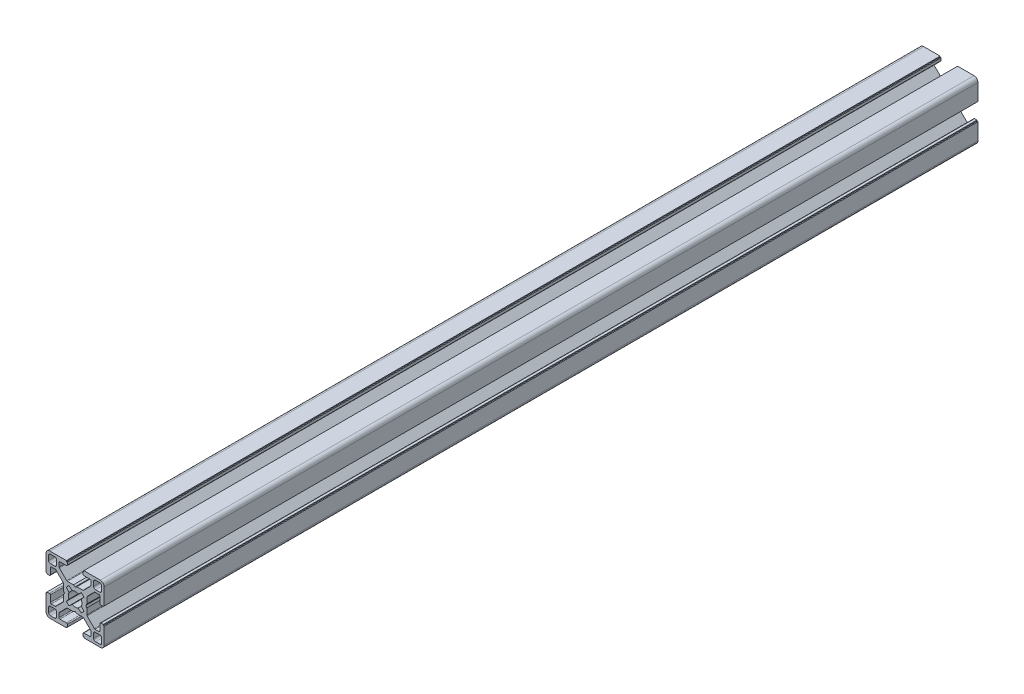
SolidWorks part; units mm, degrees
ref_plane "Front Plane" through (0, 0, 0) normal (0, 0, 1) x (1, 0, 0)
ref_plane "Top Plane" through (0, 0, 0) normal (0, 1, 0) x (1, 0, 0)
ref_plane "Right Plane" through (0, 0, 0) normal (1, 0, 0) x (0, 0, -1)
sketch "Sketch1" plane through (0, 0, 0) normal (0, 0, 1) x (1, 0, 0)
  line L0 (-15, 0) -> (15, 0) construction
  line L1 (0, -15) -> (0, 15) construction
  line L2 (-4.5, 15) -> (4.5, 15) construction
  line L3 (-4, -15) -> (4, -15) construction
  line L4 (-4.5, 15) -> (-4.5, 14.5)
  line L5 (-4.5, 14.5) -> (-4, 14.5)
  line L6 (-4, 14.5) -> (-4, 13.29)
  line L7 (-4.5, 12.79) -> (-7.7675, 12.79)
  line L8 (-8.2675, 12.29) -> (-8.2675, 10.2707)
  line L9 (-8.1211, 9.9171) -> (-4.3504, 6.1464)
  line L10 (-3.9968, 6) -> (0, 6)
  line L11 (0, 0) -> (-15, 15) construction
  line L12 (-4.5, 15) -> (-12.968, 15)
  line L14 (-12.705, 9.5135) -> (-10.5135, 9.5135)
  line L15 (-13.705, 10.5135) -> (-13.705, 12.705)
  line L16 (-12.705, 13.705) -> (-10.5135, 13.705)
  line L17 (-9.5135, 10.5135) -> (-9.5135, 12.705)
  line L18 (-13.705, 9.5135) -> (-9.5135, 13.705) construction
  line L19 (-13.705, 13.705) -> (-9.5135, 9.5135) construction
  line L20 (-3.1568, 4.5038) -> (-1.5303, 3.1477) construction
  line L21 (-4.5038, 3.1568) -> (-3.1477, 1.5303) construction
  line L22 (-6, 3.9968) -> (-6, 0)
  line L23 (-9.9171, 8.1211) -> (-6.1464, 4.3504)
  line L24 (-15, 4.5) -> (-15, 12.968)
  line L25 (-12.29, 8.2675) -> (-10.2707, 8.2675)
  line L26 (-12.79, 4.5) -> (-12.79, 7.7675)
  line L27 (-14.5, 4) -> (-13.29, 4)
  line L28 (-14.5, 4.5) -> (-14.5, 4)
  line L29 (-15, 4.5) -> (-14.5, 4.5)
  circle A0 centre (0, 0) radius 3.5
  arc A1 (-12.968, 15) -> (-15, 12.968) centre (-12.968, 12.968) ccw
  circle A2 centre (0, 0) radius 5.5 construction
  arc A3 (-10.5135, 9.5135) -> (-9.5135, 10.5135) centre (-10.5135, 10.5135) ccw
  arc A4 (-13.705, 12.705) -> (-12.705, 13.705) centre (-12.705, 12.705) cw
  arc A5 (-10.5135, 13.705) -> (-9.5135, 12.705) centre (-10.5135, 12.705) cw
  arc A6 (-12.705, 9.5135) -> (-13.705, 10.5135) centre (-12.705, 10.5135) cw
  arc A7 (-12.79, 4.5) -> (-13.29, 4) centre (-13.29, 4.5) cw
  arc A8 (-12.29, 8.2675) -> (-12.79, 7.7675) centre (-12.29, 7.7675) ccw
  arc A9 (-9.9171, 8.1211) -> (-10.2707, 8.2675) centre (-10.2707, 7.7675) ccw
  arc A10 (-6, 3.9968) -> (-6.1464, 4.3504) centre (-6.5, 3.9968) ccw
  arc A11 (-4.3504, 6.1464) -> (-3.9968, 6) centre (-3.9968, 6.5) ccw
  arc A12 (-4, 13.29) -> (-4.5, 12.79) centre (-4.5, 13.29) cw
  arc A13 (-7.7675, 12.79) -> (-8.2675, 12.29) centre (-7.7675, 12.29) ccw
  arc A14 (-8.2675, 10.2707) -> (-8.1211, 9.9171) centre (-7.7675, 10.2707) ccw
  point P4 (0, 0)
  point P8 (0, 0)
  point P13 (0, 15)
  point P15 (0, -15)
  point P16 (0, 6)
  point P23 (-11.6092, 11.6093)
  point P26 (0, 6)
  point P62 (-12.79, 4)
  point P65 (-12.79, 8.2675)
  point P68 (-10.0636, 8.2675)
  point P71 (-6, 4.2039)
  point P74 (-4.2039, 6)
  point P77 (-4, 12.79)
  point P80 (-8.2675, 12.79)
  point P83 (-8.2675, 10.0636)
  dimension "Center Hole Diameter" = 7
  dimension "D11" = 2.032
  dimension "D9" = 11
  dimension "D13" = 1
  dimension "D14" = 0.5
  dimension "Rail Height" = 30
  dimension "Rail Width" = 30
  dimension "T-Slot Width" = 8
  dimension "T-Slot Depth" = 9
  dimension "D1" = 9
  dimension "D2" = 45
  dimension "D3" = 8
  dimension "D4" = 2.21
  dimension "D5" = 16.535
  dimension "D7" = 2.54
  dimension "D6" = 1.295
  dimension "D8" = 1.246
  dimension "D10" = 10.36
  dimension "D12" = 1.905
sketch "Sketch2" plane through (0, 0, 0) normal (1, 0, 0) x (0, 0, -1)
  line L0 (-76.2, 0) -> (76.2, 0) construction
  line L2 (0, -15) -> (0, 15) construction
  line L3 (0, -15) -> (0, 15) construction
  line L4 (-76.2, -15) -> (-76.2, 15) construction
  line L5 (76.2, -15) -> (76.2, 15) construction
  point P0 (-38.7, 0)
  point P3 (0, 0)
  point P4 (38.7, 0)
  point P12 (-76.2, 0)
  point P14 (76.2, 0)
  dimension "Length" = 152.4
  dimension "D1" = 37.5
sketch "Sketch3" plane through (0, 0, 0) normal (0, 0, 1) x (1, 0, 0)
  line L0 (-4.5038, 3.1568) -> (-3.1477, 1.5303)
  line L1 (0, 3.5) -> (0, 5.5)
  line L2 (-5.5, 0) -> (-3.5, 0)
  line L7 (-6, 3.9968) -> (-6, 0) construction
  line L31 (-9.9171, 8.1211) -> (-6.1464, 4.3504) construction
  line L117 (-12.29, 8.2675) -> (-10.2707, 8.2675) construction
  line L118 (-12.79, 4.5) -> (-12.79, 7.7675) construction
  line L157 (-12.705, 9.5135) -> (-10.5135, 9.5135)
  line L158 (-9.5135, 10.5135) -> (-9.5135, 12.705)
  line L163 (-10.5135, 13.705) -> (-12.705, 13.705)
  line L164 (-13.705, 12.705) -> (-13.705, 10.5135)
  line L165 (-12.705, 9.5135) -> (-10.5135, 9.5135)
  line L166 (-9.5135, 10.5135) -> (-9.5135, 12.705)
  line L167 (-10.5135, 13.705) -> (-12.705, 13.705)
  line L168 (-13.705, 12.705) -> (-13.705, 10.5135)
  line L169 (-14.5, 4) -> (-13.29, 4) construction
  line L170 (-14.5, 4.5) -> (-14.5, 4) construction
  line L171 (-15, 4.5) -> (-14.5, 4.5) construction
  line L172 (-15, 4.5) -> (-15, 12.968) construction
  line L173 (-4.5, 15) -> (-12.968, 15) construction
  line L174 (-4.5, 15) -> (-4.5, 14.5) construction
  line L175 (-4.5, 14.5) -> (-4, 14.5) construction
  line L176 (-4, 14.5) -> (-4, 13.29) construction
  line L177 (-4.5, 12.79) -> (-7.7675, 12.79) construction
  line L178 (-8.2675, 12.29) -> (-8.2675, 10.2707) construction
  line L179 (-8.1211, 9.9171) -> (-4.3504, 6.1464) construction
  line L180 (-3.9968, 6) -> (0, 6) construction
  line L181 (-6, 3.9968) -> (-6, 0.866)
  line L182 (-9.9171, 8.1211) -> (-6.1464, 4.3504)
  line L183 (-12.29, 8.2675) -> (-10.2707, 8.2675)
  line L184 (-12.79, 4.5) -> (-12.79, 7.7675)
  line L185 (-14.5, 4) -> (-13.29, 4)
  line L186 (-14.5, 4.5) -> (-14.5, 4)
  line L187 (-15, 4.5) -> (-14.5, 4.5)
  line L188 (-15, 4.5) -> (-15, 12.968)
  line L189 (-4.5, 15) -> (-12.968, 15)
  line L190 (-4.5, 15) -> (-4.5, 14.5)
  line L191 (-4.5, 14.5) -> (-4, 14.5)
  line L192 (-4, 14.5) -> (-4, 13.29)
  line L193 (-4.5, 12.79) -> (-7.7675, 12.79)
  line L194 (-8.2675, 12.29) -> (-8.2675, 10.2707)
  line L195 (-8.1211, 9.9171) -> (-4.3504, 6.1464)
  line L196 (-3.9968, 6) -> (-0.866, 6)
  line L197 (-0.866, 6) -> (0, 5.5)
  line L198 (0, -15) -> (0, 15) construction
  line L199 (0, 0) -> (-15, 15) construction
  line L200 (0, 0) -> (-15, 15) construction
  line L201 (-3.1568, 4.5038) -> (-1.5303, 3.1477) construction
  line L202 (-3.1568, 4.5038) -> (-1.5303, 3.1477)
  line L203 (-6, 0.866) -> (-5.5, 0)
  line L204 (-15, 0) -> (15, 0) construction
  line L205 (-15, 0) -> (15, 0) construction
  line L206 (0, -15) -> (0, 15) construction
  arc A0 (-3.5, 0) -> (-3.1477, 1.5303) centre (0, 0) cw
  arc A10 (-6, 3.9968) -> (-6.1464, 4.3504) centre (-6.5, 3.9968) ccw construction
  circle A16 centre (0, 0) radius 3.5
  arc A18 (0, 3.5) -> (-1.5303, 3.1477) centre (0, 0) ccw
  arc A20 (-9.9171, 8.1211) -> (-10.2707, 8.2675) centre (-10.2707, 7.7675) ccw construction
  arc A22 (-12.29, 8.2675) -> (-12.79, 7.7675) centre (-12.29, 7.7675) ccw construction
  arc A28 (-13.29, 4) -> (-12.79, 4.5) centre (-13.29, 4.5) ccw construction
  arc A29 (-10.5135, 9.5135) -> (-9.5135, 10.5135) centre (-10.5135, 10.5135) ccw
  arc A30 (-9.5135, 12.705) -> (-10.5135, 13.705) centre (-10.5135, 12.705) ccw
  arc A31 (-12.705, 13.705) -> (-13.705, 12.705) centre (-12.705, 12.705) ccw
  arc A32 (-13.705, 10.5135) -> (-12.705, 9.5135) centre (-12.705, 10.5135) ccw
  arc A33 (-10.5135, 9.5135) -> (-9.5135, 10.5135) centre (-10.5135, 10.5135) ccw
  arc A34 (-9.5135, 12.705) -> (-10.5135, 13.705) centre (-10.5135, 12.705) ccw
  arc A35 (-12.705, 13.705) -> (-13.705, 12.705) centre (-12.705, 12.705) ccw
  arc A36 (-13.705, 10.5135) -> (-12.705, 9.5135) centre (-12.705, 10.5135) ccw
  arc A37 (-12.968, 15) -> (-15, 12.968) centre (-12.968, 12.968) ccw construction
  arc A38 (-4.5, 12.79) -> (-4, 13.29) centre (-4.5, 13.29) ccw construction
  arc A39 (-7.7675, 12.79) -> (-8.2675, 12.29) centre (-7.7675, 12.29) ccw construction
  arc A40 (-8.2675, 10.2707) -> (-8.1211, 9.9171) centre (-7.7675, 10.2707) ccw construction
  arc A41 (-4.3504, 6.1464) -> (-3.9968, 6) centre (-3.9968, 6.5) ccw construction
  arc A42 (-6, 3.9968) -> (-6.1464, 4.3504) centre (-6.5, 3.9968) ccw
  arc A43 (-9.9171, 8.1211) -> (-10.2707, 8.2675) centre (-10.2707, 7.7675) ccw
  arc A44 (-12.29, 8.2675) -> (-12.79, 7.7675) centre (-12.29, 7.7675) ccw
  arc A45 (-13.29, 4) -> (-12.79, 4.5) centre (-13.29, 4.5) ccw
  arc A46 (-12.968, 15) -> (-15, 12.968) centre (-12.968, 12.968) ccw
  arc A47 (-4.5, 12.79) -> (-4, 13.29) centre (-4.5, 13.29) ccw
  arc A48 (-7.7675, 12.79) -> (-8.2675, 12.29) centre (-7.7675, 12.29) ccw
  arc A49 (-8.2675, 10.2707) -> (-8.1211, 9.9171) centre (-7.7675, 10.2707) ccw
  arc A50 (-4.3504, 6.1464) -> (-3.9968, 6) centre (-3.9968, 6.5) ccw
  circle A51 centre (0, 0) radius 5.5 construction
  arc A52 (-3.1568, 4.5038) -> (-4.5038, 3.1568) centre (0, 0) ccw
  dimension "D3" = 60
  dimension "D4" = 60
  dimension "D1" = 0
  dimension "D2" = 0
extrude "Boss-Extrude1" add sketch "Sketch3" along normal mid plane 450
pattern_circular "CirPattern1" count 4 over 360 about axis through (0, 0, 76.2) along (0, 0, -1) of "Boss-Extrude1"
ref_plane "Contact Plane1" through (15, 0, 0) normal (1, 0, 0) x (0, 0, -1)
ref_plane "Contact Plane2" through (0, -15, 0) normal (0, 1, 0) x (1, 0, 0)
ref_plane "Contact Plane3" through (-15, 0, 0) normal (1, 0, 0) x (0, 0, -1)
ref_plane "Contact Plane4" through (0, 15, 0) normal (0, 1, 0) x (1, 0, 0)
equation "\"D1@Sketch2\" = \"Rail Height@Sketch1\" * 1.25"
equation "\"D1@Sketch1\"=\"T-Slot Width@Sketch1\"+1mm"
equation "\"D3@Sketch1\"=\"T-Slot Width@Sketch1\""
equation "\"D1@Boss-Extrude1\"=\"Length\""
equation "\"Length\"= 450mm"
